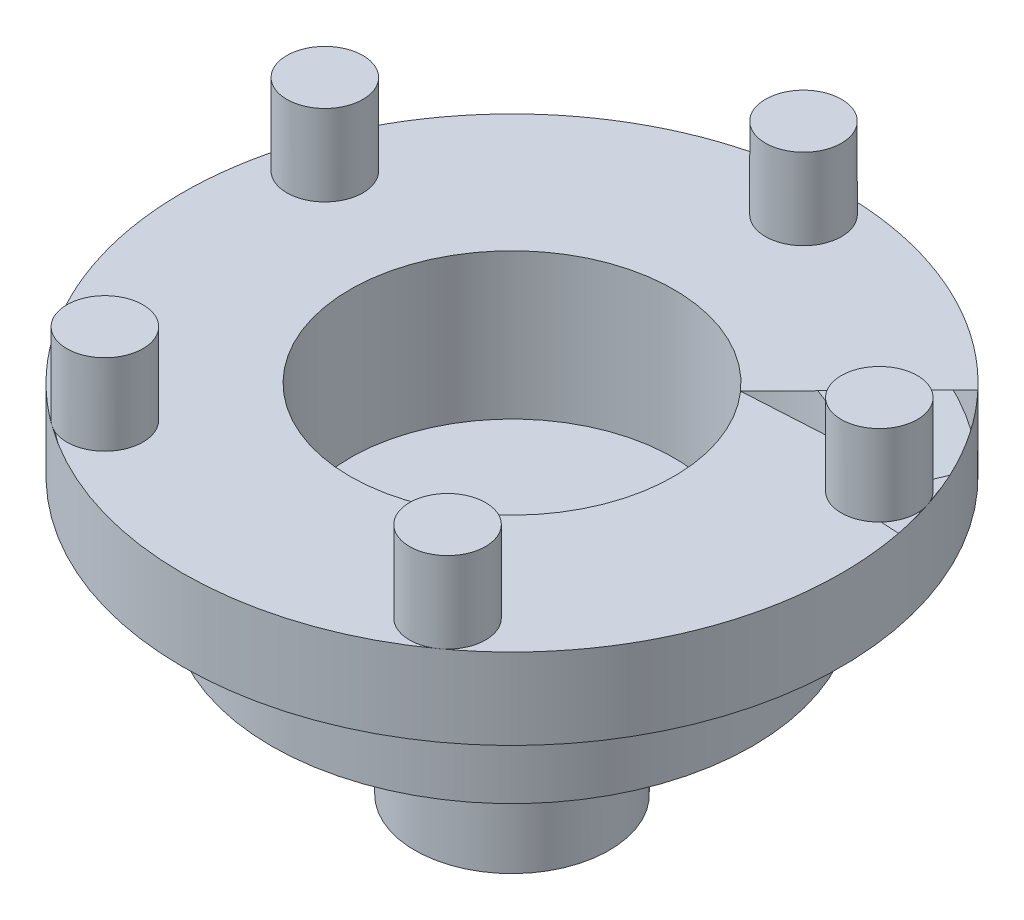
SolidWorks part; units mm, degrees
ref_plane "Front Plane" through (0, 0, 0) normal (0, 0, 1) x (1, 0, 0)
ref_plane "Top Plane" through (0, 0, 0) normal (0, 1, 0) x (1, 0, 0)
ref_plane "Right Plane" through (0, 0, 0) normal (1, 0, 0) x (0, 0, -1)
sketch "Sketch1" plane through (0, 0, 0) normal (0, 1, 0) x (1, 0, 0)
  line L0 (0, 0) -> (0, 18) construction
  circle A1 centre (0, 18) radius 2.35
  circle A2 centre (17.119, 5.5623) radius 2.35
  circle A3 centre (10.5801, -14.5623) radius 2.35
  circle A4 centre (-10.5801, -14.5623) radius 2.35
  circle A5 centre (-17.119, 5.5623) radius 2.35
  circle A6 centre (0, 0) radius 20.35
  point P15 (0, 0)
  dimension "D1" = 5
  dimension "D3" = 4.7
  dimension "D2" = 18
extrude "Boss-Extrude2" add sketch "Sketch1" along normal blind 5 contours A3 A6 A2 A1 A5 A4 | A4 | A5 | A1 | A2 | A3 region at (0, 0, -18) region at (-17.119, 0, -5.5623) region at (-10.5801, 0, 14.5623) region at (10.5801, 0, 14.5623) region at (17.119, 0, -5.5623) region at (0, 0, 0)
extrude "Boss-Extrude3" add sketch "Sketch1<3>" along normal blind 10 contours A5 | A4 | A3 | A2 | A1 region at (0, 0, -18) region at (-17.119, 0, -5.5623) region at (-10.5801, 0, 14.5623) region at (10.5801, 0, 14.5623) region at (17.119, 0, -5.5623)
sketch "Sketch1<3>" plane through (0, 0, 0) normal (0, 1, 0) x (1, 0, 0) same geometry as "Sketch1"
sketch "Sketch2" plane through (0, 0, 0) normal (0, -1, 0) x (1, 0, 0)
  circle A0 centre (0, 0) radius 14.85
  dimension "D1" = 29.7
extrude "Boss-Extrude4" add sketch "Sketch2" along normal blind 7
sketch "Sketch3" plane through (0, -7, 0) normal (0, -1, 0) x (1, 0, 0)
  circle A0 centre (0, 0) radius 6
  circle A1 centre (0, 0) radius 4.1
  dimension "D1" = 12
  dimension "D2" = 8.2
extrude "Boss-Extrude5" add sketch "Sketch3" along normal blind 10
sketch "Sketch5" plane through (0, 0, 0) normal (1, 0, 0) x (0, 0, -1)
  circle A0 centre (0, -11.9417) radius 1.6
  dimension "D1" = 3.2
extrude "Cut-Extrude1" cut sketch "Sketch5" against normal through all both and the other way through all
sketch "Sketch6" plane through (0, 5, 0) normal (0, 1, 0) x (1, 0, 0)
  circle A0 centre (0, 0) radius 10
  dimension "D1" = 20
extrude "Cut-Extrude2" cut sketch "Sketch6" against normal blind 9
